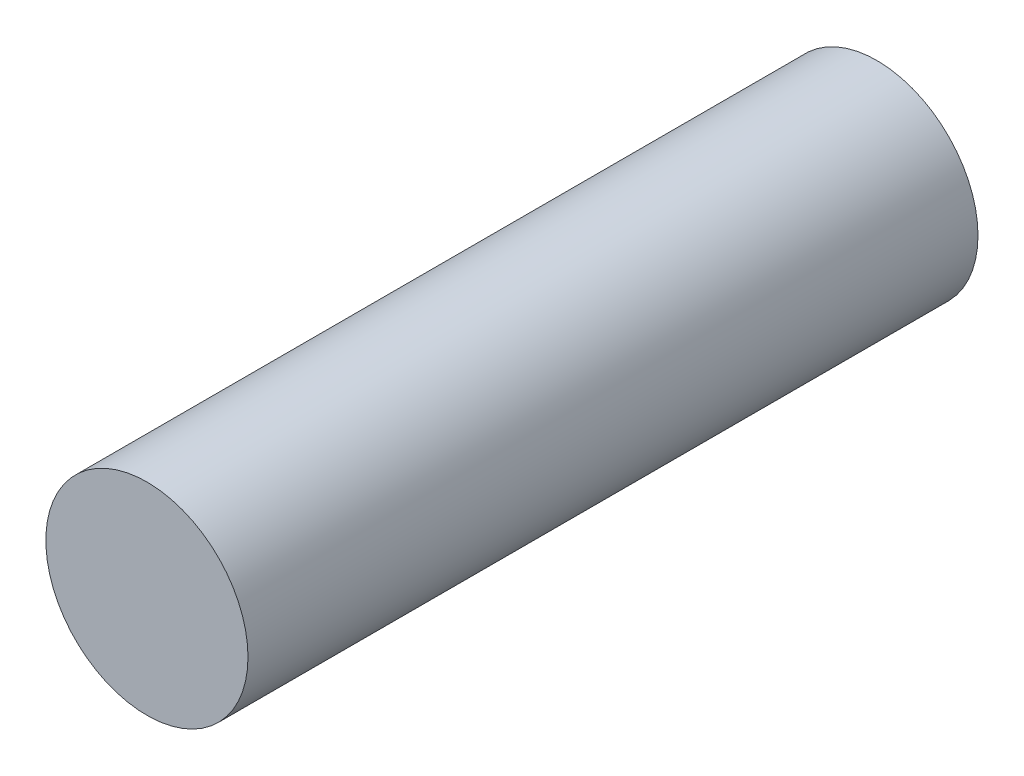
SolidWorks part; units mm, degrees
ref_plane "前视基准面" through (0, 0, 0) normal (0, 0, 1) x (1, 0, 0)
ref_plane "上视基准面" through (0, 0, 0) normal (0, 1, 0) x (1, 0, 0)
ref_plane "右视基准面" through (0, 0, 0) normal (1, 0, 0) x (0, 0, -1)
other "Configuration Table"
sketch "Sketch1" plane through (0, 0, 0) normal (0, 0, 1) x (1, 0, 0)
  circle A0 centre (0, 0) radius 9
extrude "Boss-Extrude1" add sketch "Sketch1" along normal blind 65
sketch3d "3DSketch1"
  line L0 (0, 0, 0) -> (0, 0, 65) construction
ref_axis "axis_center" through (0, 0, 0) along (0, 0, 1)
ref_plane "face_bottom_neg" through (0, 0, 0) normal (0, 0, 1) x (1, 0, 0)
ref_plane "face_top_pos" through (0, 0, 65) normal (0, 0, 1) x (1, 0, 0)
